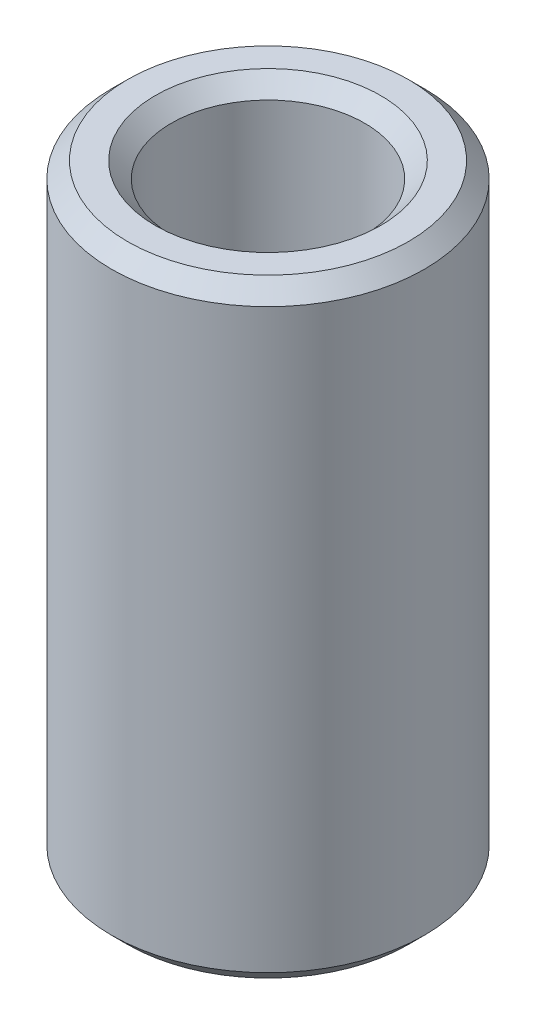
SolidWorks part; units mm, degrees
ref_plane "Front Plane" through (0, 0, 0) normal (0, 0, 1) x (1, 0, 0)
ref_plane "Top Plane" through (0, 0, 0) normal (0, 1, 0) x (1, 0, 0)
ref_plane "Right Plane" through (0, 0, 0) normal (1, 0, 0) x (0, 0, -1)
sketch "Sketch1" plane through (0, 0, 0) normal (0, 1, 0) x (1, 0, 0)
  circle A0 centre (0, 0) radius 37.5
  dimension "SLEEVE_OD" = 75
extrude "Boss-Extrude1" add sketch "Sketch1" along normal blind 145.9566
sketch "Sketch2" plane through (0, 0, 0) normal (0, 1, 0) x (1, 0, 0)
  circle A0 centre (0, 0) radius 23.1869
  dimension "BORE_D" = 46.3738
extrude "Cut-Extrude1" cut sketch "Sketch2" along normal through all
chamfer "Chamfer1" distance 3.8315 angle 45 4 edges at (0, 145.9566, 23.1869) (0, 0, 23.1869) (0, 0, 37.5) (0, 145.9566, 37.5)
